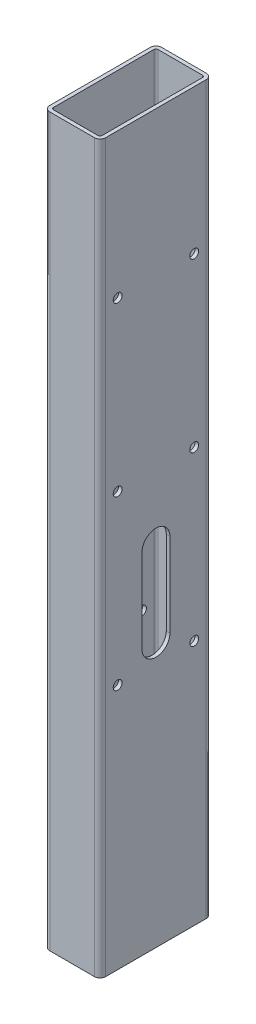
SolidWorks part; units mm, degrees
material "6061-T6 (SS)"
ref_plane "Front Plane" through (0, 0, 0) normal (0, 0, 1) x (1, 0, 0)
ref_plane "Top Plane" through (0, 0, 0) normal (0, 1, 0) x (1, 0, 0)
ref_plane "Right Plane" through (0, 0, 0) normal (1, 0, 0) x (0, 0, -1)
sketch "Sketch1" plane through (0, 0, 0) normal (0, 1, 0) x (1, 0, 0)
  line L1 (10.16, -25.4) -> (-10.16, -25.4)
  line L2 (12.7, -22.86) -> (12.7, 22.86)
  line L3 (10.16, 25.4) -> (-10.16, 25.4)
  line L4 (-12.7, -22.86) -> (-12.7, 22.86)
  line L5 (12.7, -25.4) -> (-12.7, 25.4) construction
  line L6 (12.7, 25.4) -> (-12.7, -25.4) construction
  arc A0 (-10.16, -25.4) -> (-12.7, -22.86) centre (-10.16, -22.86) cw
  arc A1 (10.16, -25.4) -> (12.7, -22.86) centre (10.16, -22.86) ccw
  arc A2 (12.7, 22.86) -> (10.16, 25.4) centre (10.16, 22.86) ccw
  arc A3 (-10.16, 25.4) -> (-12.7, 22.86) centre (-10.16, 22.86) ccw
  point P0 (0, 0)
  dimension "D3" = 2.54
  dimension "D1" = 25.4
  dimension "D2" = 50.8
extrude "Extrude-Thin1" add sketch "Sketch1" against normal blind 330.2 thin thin type one direction reverse wall 1.651
sketch "Sketch2" plane through (-12.7, 0, 0) normal (-1, 0, 0) x (0, 0, 1)
  line L0 (0, -74.3995) -> (0, -209.55) construction
  line L4 (2.5527, -74.3995) -> (2.5527, -209.55)
  line L5 (-2.5527, -74.3995) -> (-2.5527, -209.55)
  line L6 (-263.9645, -355.6) -> (-128.814, -355.6) construction
  line L7 (-128.814, -355.6) -> (0, -79.3574) construction
  line L8 (0, -203.2) -> (-263.9645, -355.6) construction
  line L9 (-22.86, -330.2) -> (22.86, -330.2) construction
  arc A2 (2.5527, -74.3995) -> (-2.5527, -74.3995) centre (0, -74.3995) ccw
  arc A3 (-2.5527, -209.55) -> (2.5527, -209.55) centre (0, -209.55) ccw
  point P3 (0, -141.9748)
  dimension "D5" = 5.1054
  dimension "D1" = 25.4
  dimension "D2" = 65
  dimension "D3" = 30
  dimension "D4" = 304.8
  dimension "D6" = 6.35
extrude "Cut-Extrude1" cut sketch "Sketch2" against normal up to next
sketch "Sketch5" plane through (12.7, 0, 0) normal (1, 0, 0) x (0, 0, -1)
  line L0 (0, -171.45) -> (0, -209.55) construction
  line L1 (6.35, -171.45) -> (6.35, -209.55)
  line L2 (-6.35, -171.45) -> (-6.35, -209.55)
  arc A0 (6.35, -171.45) -> (-6.35, -171.45) centre (0, -171.45) ccw
  arc A1 (-6.35, -209.55) -> (6.35, -209.55) centre (0, -209.55) ccw
  point P2 (0, -190.5)
  dimension "D1" = 6.35
  dimension "D2" = 38.1
extrude "Cut-Extrude4" cut sketch "Sketch5" against normal up to next
sketch "Sketch4" plane through (12.7, 0, 0) normal (1, 0, 0) x (0, 0, -1)
  circle A0 centre (-17.399, -218.1748) radius 2.0193 construction
  circle A1 centre (17.399, -218.1748) radius 2.0193 construction
  circle A2 centre (-17.399, -141.9748) radius 2.0193 construction
  circle A3 centre (17.399, -141.9748) radius 2.0193 construction
  circle A4 centre (-17.399, -65.7748) radius 2.0193 construction
  circle A5 centre (17.399, -65.7748) radius 2.0193 construction
  circle A6 centre (-17.399, -218.1748) radius 2.0193
  circle A7 centre (17.399, -218.1748) radius 2.0193
  circle A8 centre (-17.399, -141.9748) radius 2.0193
  circle A9 centre (17.399, -141.9748) radius 2.0193
  circle A10 centre (-17.399, -65.7748) radius 2.0193
  circle A11 centre (17.399, -65.7748) radius 2.0193
extrude "Cut-Extrude3" cut sketch "Sketch4" against normal through all
